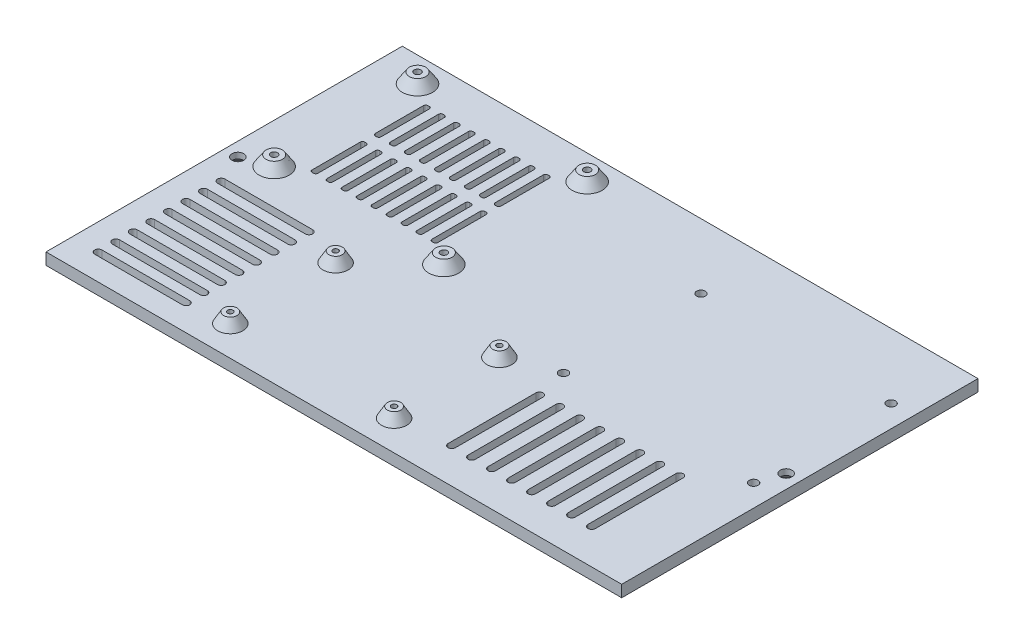
SolidWorks part; units mm, degrees
ref_plane "Front Plane" through (0, 0, 0) normal (0, 0, 1) x (1, 0, 0)
ref_plane "Top Plane" through (0, 0, 0) normal (0, 1, 0) x (1, 0, 0)
ref_plane "Right Plane" through (0, 0, 0) normal (1, 0, 0) x (0, 0, -1)
sketch "Sketch1" plane through (0, 0, 0) normal (0, 1, 0) x (1, 0, 0)
  line L1 (-98.4, 60.9) -> (98.4, 60.9)
  line L2 (-98.4, 60.9) -> (-98.4, -60.9)
  line L3 (-98.4, -60.9) -> (98.4, -60.9)
  line L4 (98.4, 60.9) -> (98.4, -60.9)
  line L5 (-98.4, 60.9) -> (98.4, -60.9) construction
  line L6 (-98.4, -60.9) -> (98.4, 60.9) construction
  point P0 (0, 0)
  dimension "D1" = 121.8
  dimension "D2" = 196.8
extrude "Boss-Extrude1" add sketch "Sketch1" along normal blind 4
sketch "Sketch2" plane through (0, 0, 0) normal (0, -1, 0) x (-1, 0, 0)
  line L0 (98.4, 60.9) -> (98.4, -60.9) construction
  circle A0 centre (93.7, 0) radius 2
  dimension "D2" = 4
  dimension "D1" = 4.7
extrude "Cut-Extrude1" cut sketch "Sketch2" against normal through all and the other way through all
hole_wizard "CSK for M4 Hex Socket Countersunk Head Screw3" positions "3DSketch1" profile "Sketch4" countersink size "M4" standard "DIN" end condition through all
sketch3d "3DSketch1"
  line L0 (-93.7, 4, 0) -> (-93.7, 0, 0) construction
  point P0 (-93.7, 0, 0)
sketch "Sketch4" plane through (-93.7, 0, 0) normal (1, 0, 0) x (0, 0, -1)
  line L0 (0, 0) -> (0, 4)
  line L1 (0, 4) -> (2, 4)
  line L2 (2, 4) -> (2, 2)
  line L3 (2, 2) -> (4, 0)
  line L5 (4, 0) -> (0, 0)
  line L6 (-2, 2) -> (-4, 0) construction
  line L11 (0, -6.35) -> (0, 107.95) construction
  dimension "Thru Hole Dia." = 4
  dimension "Thru Hole Depth" = 4
  dimension "Near C'Sink Dia." = 8
  dimension "Near C'Sink Angle" = 90
mirror "Mirror1" about plane through (0, 0, 0) normal (1, 0, 0) of "CSK for M4 Hex Socket Countersunk Head Screw3", "Cut-Extrude1"
sketch "Sketch6" plane through (0, 4, 0) normal (0, 1, 0) x (1, 0, 0)
  line L4 (98.4, 60.9) -> (-98.4, 60.9) construction
  line L5 (-98.4, 60.9) -> (-98.4, -60.9) construction
  circle A0 centre (-26.7, 3.4) radius 2.75
  circle A1 centre (-84.7, 3.4) radius 2.75
  circle A2 centre (-26.7, 52.4) radius 2.75
  circle A3 centre (-84.7, 52.4) radius 2.75
  line B0 (-88.2, 55.9) -> (-88.2, -0.1) construction
  line B1 (-88.2, -0.1) -> (-0.828, -0.1) construction
  line B2 (-0.828, -0.1) -> (-0.828, 55.9) construction
  line B3 (-0.828, 55.9) -> (-88.2, 55.9) construction
  circle B4 centre (-84.7, 52.4) radius 1.6
  circle B5 centre (-26.7, 52.4) radius 1.6
  circle B6 centre (-84.7, 3.4) radius 1.6
  circle B7 centre (-26.7, 3.4) radius 1.6
  dimension "D3" = 5.5
  dimension "D1" = 5
  dimension "D2" = 10.2
sketch_block_instance "Raspberry_Pi_3-1"
sketch_block "Raspberry_Pi_3" parameters "D11"=3.2, "D1"=87.372, "D2"=56, "D3"=3.5, "D4"=3.5, "D5"=3.5, "D6"=3.5, "D7"=3.5, "D8"=3.5, "D9"=58, "D10"=58
extrude "Boss-Extrude3" add sketch "Sketch6" along normal blind 3.5 contours A2 | A0 | A1 | A3
chamfer "Chamfer1" distance 2.4 angle 56 4 edges at (-84.7, 4, -49.65) (-26.7, 4, -49.65) (-84.7, 4, -0.65) (-26.7, 4, -0.65) first distance on face at (-84.7, 4, -49.65)
sketch "Sketch7" plane through (0, 7.5, 0) normal (0, 1, 0) x (1, 0, 0)
  circle A0 centre (-26.7, 3.4) radius 1.16
  circle A1 centre (-26.7, 52.4) radius 1.16
  circle A2 centre (-84.7, 52.4) radius 1.16
  circle A3 centre (-84.7, 3.4) radius 1.16
  dimension "D1" = 2.32
extrude "Cut-Extrude2" cut sketch "Sketch7" against normal blind 6.5
sketch "Sketch8" plane through (0, 4, 0) normal (0, 1, 0) x (1, 0, 0)
  circle A4 centre (-84.7, 3.4) radius 1.16 construction
  circle A5 centre (-26.7, 3.4) radius 1.16 construction
  circle A6 centre (-45.7, -14.6) radius 2.25
  circle A7 centre (10.3, -14.6) radius 2.25
  circle A8 centre (10.3, -50.6) radius 2.25
  circle A9 centre (-45.7, -50.6) radius 2.25
  circle B0 centre (-45.7, -50.6) radius 1
  circle B1 centre (-45.7, -14.6) radius 1
  circle B2 centre (10.3, -50.6) radius 1
  circle B3 centre (10.3, -14.6) radius 1
  line B4 (-47.7, -52.6) -> (-47.7, -12.6)
  line B5 (-47.7, -52.6) -> (12.3, -52.6)
  line B6 (-47.7, -12.6) -> (12.3, -12.6)
  line B7 (12.3, -52.6) -> (12.3, -12.6)
  line B8 (-47.7, -52.6) -> (12.3, -12.6) construction
  line B9 (12.3, -52.6) -> (-47.7, -12.6) construction
  dimension "D3" = 4.5
  dimension "D1" = 16
  dimension "D2" = 37
sketch_block_instance "Block1-1"
sketch_block "Block1" parameters "D3"=2, "D1"=36, "D2"=56, "D4"=27.8378, "D5"=16.8829, "D6"=53.5192, "D7"=78.3779
extrude "Boss-Extrude4" add sketch "Sketch8" along normal blind 3.5 contours A9 | A6 | A7 | A8
chamfer "Chamfer2" distance 2.05 angle 60 4 edges at (10.3, 4, 16.85) (10.3, 4, 52.85) (-45.7, 4, 52.85) (-45.7, 4, 16.85) first distance on face at (10.3, 4, 52.85)
sketch "Sketch9" plane through (0, 7.5, 0) normal (0, 1, 0) x (1, 0, 0)
  circle A0 centre (-45.7, -14.6) radius 0.93
  circle A1 centre (10.3, -14.6) radius 0.93
  circle A2 centre (10.3, -50.6) radius 0.93
  circle A3 centre (-45.7, -50.6) radius 0.93
  dimension "D1" = 1.86
extrude "Cut-Extrude3" cut sketch "Sketch9" against normal blind 6.5
sketch "Sketch10" plane through (0, 4, 0) normal (0, 1, 0) x (1, 0, 0)
  line L0 (98.4, 60.9) -> (-98.4, 60.9) construction
  line L1 (89.4, 60.7) -> (27.4, 60.7)
  line L2 (89.4, 60.7) -> (89.4, -30.3)
  line L3 (89.4, -30.3) -> (27.4, -30.3)
  line L4 (27.4, 60.7) -> (27.4, -30.3)
  line L5 (98.4, -60.9) -> (98.4, 60.9) construction
  circle A0 centre (25.9, 38.7) radius 1.5
  circle A1 centre (25.9, -8.3) radius 1.5
  circle A2 centre (90.9, -8.3) radius 1.5
  circle A3 centre (90.9, 38.7) radius 1.5
  dimension "D5" = 3
  dimension "D1" = 62
  dimension "D2" = 91
  dimension "D3" = 0.2
  dimension "D4" = 9
  dimension "D6" = 22
  dimension "D7" = 22
extrude "Cut-Extrude4" cut sketch "Sketch10" against normal through all contours A0 | A1 | A2 | A3 region at (90.9, 4, -38.7) region at (90.9, 4, 8.3) region at (25.9, 4, 8.3) region at (25.9, 4, -38.7)
sketch "Sketch11" plane through (0, 4, 0) normal (0, 1, 0) x (1, 0, 0)
  line L1 (-76.45, 47.7) -> (-75.95, 47.7)
  line L2 (-77.2, 46.95) -> (-77.2, 30.45)
  line L3 (-76.45, 29.7) -> (-75.95, 29.7)
  line L4 (-75.2, 46.95) -> (-75.2, 30.45)
  line L5 (-72.075, 46.95) -> (-72.075, 30.45)
  line L6 (-71.325, 47.7) -> (-70.825, 47.7)
  line L7 (-70.075, 46.95) -> (-70.075, 30.45)
  line L8 (-71.325, 29.7) -> (-70.825, 29.7)
  line L9 (-66.95, 46.95) -> (-66.95, 30.45)
  line L10 (-66.2, 47.7) -> (-65.7, 47.7)
  line L11 (-64.95, 46.95) -> (-64.95, 30.45)
  line L12 (-66.2, 29.7) -> (-65.7, 29.7)
  line L13 (-61.825, 46.95) -> (-61.825, 30.45)
  line L14 (-61.075, 47.7) -> (-60.575, 47.7)
  line L15 (-59.825, 46.95) -> (-59.825, 30.45)
  line L16 (-61.075, 29.7) -> (-60.575, 29.7)
  line L17 (-56.7, 46.95) -> (-56.7, 30.45)
  line L18 (-55.95, 47.7) -> (-55.45, 47.7)
  line L19 (-54.7, 46.95) -> (-54.7, 30.45)
  line L20 (-55.95, 29.7) -> (-55.45, 29.7)
  line L21 (-51.575, 46.95) -> (-51.575, 30.45)
  line L22 (-50.825, 47.7) -> (-50.325, 47.7)
  line L23 (-49.575, 46.95) -> (-49.575, 30.45)
  line L24 (-50.825, 29.7) -> (-50.325, 29.7)
  line L25 (-46.45, 46.95) -> (-46.45, 30.45)
  line L26 (-45.7, 47.7) -> (-45.2, 47.7)
  line L27 (-44.45, 46.95) -> (-44.45, 30.45)
  line L28 (-45.7, 29.7) -> (-45.2, 29.7)
  line L29 (-41.325, 46.95) -> (-41.325, 30.45)
  line L30 (-40.575, 47.7) -> (-40.075, 47.7)
  line L31 (-39.325, 46.95) -> (-39.325, 30.45)
  line L32 (-40.575, 29.7) -> (-40.075, 29.7)
  line L33 (-36.2, 46.95) -> (-36.2, 30.45)
  line L34 (-35.45, 47.7) -> (-34.95, 47.7)
  line L35 (-34.2, 46.95) -> (-34.2, 30.45)
  line L36 (-35.45, 29.7) -> (-34.95, 29.7)
  line L37 (-72.075, 25.35) -> (-72.075, 8.85)
  line L38 (-71.325, 26.1) -> (-70.825, 26.1)
  line L39 (-70.075, 25.35) -> (-70.075, 8.85)
  line L40 (-71.325, 8.1) -> (-70.825, 8.1)
  line L41 (-66.95, 25.35) -> (-66.95, 8.85)
  line L42 (-66.2, 26.1) -> (-65.7, 26.1)
  line L43 (-64.95, 25.35) -> (-64.95, 8.85)
  line L44 (-66.2, 8.1) -> (-65.7, 8.1)
  line L45 (-61.825, 25.35) -> (-61.825, 8.85)
  line L46 (-61.075, 26.1) -> (-60.575, 26.1)
  line L47 (-59.825, 25.35) -> (-59.825, 8.85)
  line L48 (-61.075, 8.1) -> (-60.575, 8.1)
  line L49 (-56.7, 25.35) -> (-56.7, 8.85)
  line L50 (-55.95, 26.1) -> (-55.45, 26.1)
  line L51 (-54.7, 25.35) -> (-54.7, 8.85)
  line L52 (-55.95, 8.1) -> (-55.45, 8.1)
  line L53 (-51.575, 25.35) -> (-51.575, 8.85)
  line L54 (-50.825, 26.1) -> (-50.325, 26.1)
  line L55 (-49.575, 25.35) -> (-49.575, 8.85)
  line L56 (-50.825, 8.1) -> (-50.325, 8.1)
  line L57 (-46.45, 25.35) -> (-46.45, 8.85)
  line L58 (-45.7, 26.1) -> (-45.2, 26.1)
  line L59 (-44.45, 25.35) -> (-44.45, 8.85)
  line L60 (-45.7, 8.1) -> (-45.2, 8.1)
  line L61 (-41.325, 25.35) -> (-41.325, 8.85)
  line L62 (-40.575, 26.1) -> (-40.075, 26.1)
  line L63 (-39.325, 25.35) -> (-39.325, 8.85)
  line L64 (-40.575, 8.1) -> (-40.075, 8.1)
  line L65 (-36.2, 25.35) -> (-36.2, 8.85)
  line L66 (-35.45, 26.1) -> (-34.95, 26.1)
  line L67 (-34.2, 25.35) -> (-34.2, 8.85)
  line L68 (-35.45, 8.1) -> (-34.95, 8.1)
  line L69 (-77.2, 25.35) -> (-77.2, 8.85)
  line L70 (-76.45, 26.1) -> (-75.95, 26.1)
  line L71 (-75.2, 25.35) -> (-75.2, 8.85)
  line L72 (-76.45, 8.1) -> (-75.95, 8.1)
  arc A0 (-75.95, 47.7) -> (-75.2, 46.95) centre (-75.95, 46.95) cw
  arc A1 (-76.45, 47.7) -> (-77.2, 46.95) centre (-76.45, 46.95) ccw
  arc A2 (-75.95, 29.7) -> (-75.2, 30.45) centre (-75.95, 30.45) ccw
  arc A3 (-77.2, 30.45) -> (-76.45, 29.7) centre (-76.45, 30.45) ccw
  arc A4 (-72.075, 30.45) -> (-71.325, 29.7) centre (-71.325, 30.45) ccw
  arc A5 (-71.325, 47.7) -> (-72.075, 46.95) centre (-71.325, 46.95) ccw
  arc A6 (-70.825, 47.7) -> (-70.075, 46.95) centre (-70.825, 46.95) cw
  arc A7 (-70.825, 29.7) -> (-70.075, 30.45) centre (-70.825, 30.45) ccw
  arc A8 (-66.95, 30.45) -> (-66.2, 29.7) centre (-66.2, 30.45) ccw
  arc A9 (-66.2, 47.7) -> (-66.95, 46.95) centre (-66.2, 46.95) ccw
  arc A10 (-65.7, 47.7) -> (-64.95, 46.95) centre (-65.7, 46.95) cw
  arc A11 (-65.7, 29.7) -> (-64.95, 30.45) centre (-65.7, 30.45) ccw
  arc A12 (-61.825, 30.45) -> (-61.075, 29.7) centre (-61.075, 30.45) ccw
  arc A13 (-61.075, 47.7) -> (-61.825, 46.95) centre (-61.075, 46.95) ccw
  arc A14 (-60.575, 47.7) -> (-59.825, 46.95) centre (-60.575, 46.95) cw
  arc A15 (-60.575, 29.7) -> (-59.825, 30.45) centre (-60.575, 30.45) ccw
  arc A16 (-56.7, 30.45) -> (-55.95, 29.7) centre (-55.95, 30.45) ccw
  arc A17 (-55.95, 47.7) -> (-56.7, 46.95) centre (-55.95, 46.95) ccw
  arc A18 (-55.45, 47.7) -> (-54.7, 46.95) centre (-55.45, 46.95) cw
  arc A19 (-55.45, 29.7) -> (-54.7, 30.45) centre (-55.45, 30.45) ccw
  arc A20 (-51.575, 30.45) -> (-50.825, 29.7) centre (-50.825, 30.45) ccw
  arc A21 (-50.825, 47.7) -> (-51.575, 46.95) centre (-50.825, 46.95) ccw
  arc A22 (-50.325, 47.7) -> (-49.575, 46.95) centre (-50.325, 46.95) cw
  arc A23 (-50.325, 29.7) -> (-49.575, 30.45) centre (-50.325, 30.45) ccw
  arc A24 (-46.45, 30.45) -> (-45.7, 29.7) centre (-45.7, 30.45) ccw
  arc A25 (-45.7, 47.7) -> (-46.45, 46.95) centre (-45.7, 46.95) ccw
  arc A26 (-45.2, 47.7) -> (-44.45, 46.95) centre (-45.2, 46.95) cw
  arc A27 (-45.2, 29.7) -> (-44.45, 30.45) centre (-45.2, 30.45) ccw
  arc A28 (-41.325, 30.45) -> (-40.575, 29.7) centre (-40.575, 30.45) ccw
  arc A29 (-40.575, 47.7) -> (-41.325, 46.95) centre (-40.575, 46.95) ccw
  arc A30 (-40.075, 47.7) -> (-39.325, 46.95) centre (-40.075, 46.95) cw
  arc A31 (-40.075, 29.7) -> (-39.325, 30.45) centre (-40.075, 30.45) ccw
  arc A32 (-36.2, 30.45) -> (-35.45, 29.7) centre (-35.45, 30.45) ccw
  arc A33 (-35.45, 47.7) -> (-36.2, 46.95) centre (-35.45, 46.95) ccw
  arc A34 (-34.95, 47.7) -> (-34.2, 46.95) centre (-34.95, 46.95) cw
  arc A35 (-34.95, 29.7) -> (-34.2, 30.45) centre (-34.95, 30.45) ccw
  arc A36 (-72.075, 8.85) -> (-71.325, 8.1) centre (-71.325, 8.85) ccw
  arc A37 (-71.325, 26.1) -> (-72.075, 25.35) centre (-71.325, 25.35) ccw
  arc A38 (-70.825, 26.1) -> (-70.075, 25.35) centre (-70.825, 25.35) cw
  arc A39 (-70.825, 8.1) -> (-70.075, 8.85) centre (-70.825, 8.85) ccw
  arc A40 (-66.95, 8.85) -> (-66.2, 8.1) centre (-66.2, 8.85) ccw
  arc A41 (-66.2, 26.1) -> (-66.95, 25.35) centre (-66.2, 25.35) ccw
  arc A42 (-65.7, 26.1) -> (-64.95, 25.35) centre (-65.7, 25.35) cw
  arc A43 (-65.7, 8.1) -> (-64.95, 8.85) centre (-65.7, 8.85) ccw
  arc A44 (-61.825, 8.85) -> (-61.075, 8.1) centre (-61.075, 8.85) ccw
  arc A45 (-61.075, 26.1) -> (-61.825, 25.35) centre (-61.075, 25.35) ccw
  arc A46 (-60.575, 26.1) -> (-59.825, 25.35) centre (-60.575, 25.35) cw
  arc A47 (-60.575, 8.1) -> (-59.825, 8.85) centre (-60.575, 8.85) ccw
  arc A48 (-56.7, 8.85) -> (-55.95, 8.1) centre (-55.95, 8.85) ccw
  arc A49 (-55.95, 26.1) -> (-56.7, 25.35) centre (-55.95, 25.35) ccw
  arc A50 (-55.45, 26.1) -> (-54.7, 25.35) centre (-55.45, 25.35) cw
  arc A51 (-55.45, 8.1) -> (-54.7, 8.85) centre (-55.45, 8.85) ccw
  arc A52 (-51.575, 8.85) -> (-50.825, 8.1) centre (-50.825, 8.85) ccw
  arc A53 (-50.825, 26.1) -> (-51.575, 25.35) centre (-50.825, 25.35) ccw
  arc A54 (-50.325, 26.1) -> (-49.575, 25.35) centre (-50.325, 25.35) cw
  arc A55 (-50.325, 8.1) -> (-49.575, 8.85) centre (-50.325, 8.85) ccw
  arc A56 (-46.45, 8.85) -> (-45.7, 8.1) centre (-45.7, 8.85) ccw
  arc A57 (-45.7, 26.1) -> (-46.45, 25.35) centre (-45.7, 25.35) ccw
  arc A58 (-45.2, 26.1) -> (-44.45, 25.35) centre (-45.2, 25.35) cw
  arc A59 (-45.2, 8.1) -> (-44.45, 8.85) centre (-45.2, 8.85) ccw
  arc A60 (-41.325, 8.85) -> (-40.575, 8.1) centre (-40.575, 8.85) ccw
  arc A61 (-40.575, 26.1) -> (-41.325, 25.35) centre (-40.575, 25.35) ccw
  arc A62 (-40.075, 26.1) -> (-39.325, 25.35) centre (-40.075, 25.35) cw
  arc A63 (-40.075, 8.1) -> (-39.325, 8.85) centre (-40.075, 8.85) ccw
  arc A64 (-36.2, 8.85) -> (-35.45, 8.1) centre (-35.45, 8.85) ccw
  arc A65 (-35.45, 26.1) -> (-36.2, 25.35) centre (-35.45, 25.35) ccw
  arc A66 (-34.95, 26.1) -> (-34.2, 25.35) centre (-34.95, 25.35) cw
  arc A67 (-34.95, 8.1) -> (-34.2, 8.85) centre (-34.95, 8.85) ccw
  arc A68 (-77.2, 8.85) -> (-76.45, 8.1) centre (-76.45, 8.85) ccw
  arc A69 (-76.45, 26.1) -> (-77.2, 25.35) centre (-76.45, 25.35) ccw
  arc A70 (-75.95, 26.1) -> (-75.2, 25.35) centre (-75.95, 25.35) cw
  arc A71 (-75.95, 8.1) -> (-75.2, 8.85) centre (-75.95, 8.85) ccw
  circle A72 centre (-26.7, 52.4) radius 1.16 construction
  circle A73 centre (-84.7, 3.4) radius 1.16 construction
  circle A74 centre (-84.7, 52.4) radius 1.16 construction
  circle A75 centre (-84.7, 52.4) radius 1.16 construction
  point P11 (-75.2, 47.7)
  point P14 (-77.2, 47.7)
  point P17 (-75.2, 29.7)
  point P20 (-77.2, 29.7)
  dimension "D5" = 0.75
  dimension "D1" = 2
  dimension "D2" = 18
  dimension "D3" = 4.7
  dimension "D4" = 7.5
  dimension "D8" = 7.5
  dimension "D9" = 4.7
  dimension "D6" = 9
  dimension "D7" = 2
extrude "Cut-Extrude5" cut sketch "Sketch11" against normal through all
sketch "Sketch12" plane through (0, 4, 0) normal (0, 1, 0) x (1, 0, 0)
  line L0 (-89.4, -10) -> (-59.4, -10) construction
  line L1 (-89.4, -8.75) -> (-59.4, -8.75)
  line L2 (-89.4, -11.25) -> (-59.4, -11.25)
  line L3 (-98.4, 60.9) -> (-98.4, -60.9) construction
  line L4 (-89.4, -17.25) -> (-59.4, -17.25)
  line L5 (-89.4, -14.75) -> (-59.4, -14.75)
  line L6 (-89.4, -16) -> (-59.4, -16) construction
  line L7 (-89.4, -23.25) -> (-59.4, -23.25)
  line L8 (-89.4, -20.75) -> (-59.4, -20.75)
  line L9 (-89.4, -22) -> (-59.4, -22) construction
  line L10 (-89.4, -29.25) -> (-59.4, -29.25)
  line L11 (-89.4, -26.75) -> (-59.4, -26.75)
  line L12 (-89.4, -28) -> (-59.4, -28) construction
  line L13 (-89.4, -35.25) -> (-59.4, -35.25)
  line L14 (-89.4, -32.75) -> (-59.4, -32.75)
  line L15 (-89.4, -34) -> (-59.4, -34) construction
  line L16 (-89.4, -41.25) -> (-59.4, -41.25)
  line L17 (-89.4, -38.75) -> (-59.4, -38.75)
  line L18 (-89.4, -40) -> (-59.4, -40) construction
  line L19 (-89.4, -47.25) -> (-59.4, -47.25)
  line L20 (-89.4, -44.75) -> (-59.4, -44.75)
  line L21 (-89.4, -46) -> (-59.4, -46) construction
  line L22 (-89.4, -53.25) -> (-59.4, -53.25)
  line L23 (-89.4, -50.75) -> (-59.4, -50.75)
  line L24 (-89.4, -52) -> (-59.4, -52) construction
  arc A0 (-89.4, -8.75) -> (-89.4, -11.25) centre (-89.4, -10) ccw
  arc A1 (-59.4, -11.25) -> (-59.4, -8.75) centre (-59.4, -10) ccw
  circle A2 centre (-93.7, 0) radius 2 construction
  arc A3 (-89.4, -14.75) -> (-89.4, -17.25) centre (-89.4, -16) ccw
  arc A4 (-59.4, -17.25) -> (-59.4, -14.75) centre (-59.4, -16) ccw
  arc A5 (-89.4, -20.75) -> (-89.4, -23.25) centre (-89.4, -22) ccw
  arc A6 (-59.4, -23.25) -> (-59.4, -20.75) centre (-59.4, -22) ccw
  arc A7 (-89.4, -26.75) -> (-89.4, -29.25) centre (-89.4, -28) ccw
  arc A8 (-59.4, -29.25) -> (-59.4, -26.75) centre (-59.4, -28) ccw
  arc A9 (-89.4, -32.75) -> (-89.4, -35.25) centre (-89.4, -34) ccw
  arc A10 (-59.4, -35.25) -> (-59.4, -32.75) centre (-59.4, -34) ccw
  arc A11 (-89.4, -38.75) -> (-89.4, -41.25) centre (-89.4, -40) ccw
  arc A12 (-59.4, -41.25) -> (-59.4, -38.75) centre (-59.4, -40) ccw
  arc A13 (-89.4, -44.75) -> (-89.4, -47.25) centre (-89.4, -46) ccw
  arc A14 (-59.4, -47.25) -> (-59.4, -44.75) centre (-59.4, -46) ccw
  arc A15 (-89.4, -50.75) -> (-89.4, -53.25) centre (-89.4, -52) ccw
  arc A16 (-59.4, -53.25) -> (-59.4, -50.75) centre (-59.4, -52) ccw
  point P2 (-74.4, -10)
  point P15 (-74.4, -16)
  point P22 (-74.4, -22)
  point P29 (-74.4, -28)
  point P36 (-74.4, -34)
  point P43 (-74.4, -40)
  point P50 (-74.4, -46)
  point P57 (-74.4, -52)
  dimension "D1" = 2.5
  dimension "D2" = 30
  dimension "D3" = 9
  dimension "D4" = 10
  dimension "D5" = 8
extrude "Cut-Extrude6" cut sketch "Sketch12" against normal through all
sketch "Sketch13" plane through (0, 4, 0) normal (0, 1, 0) x (1, 0, 0)
  line L0 (28.3, -18.9) -> (28.3, -48.9) construction
  line L1 (29.55, -18.9) -> (29.55, -48.9)
  line L2 (27.05, -18.9) -> (27.05, -48.9)
  line L3 (-98.4, -60.9) -> (98.4, -60.9) construction
  line L4 (33.8857, -18.9) -> (33.8857, -48.9)
  line L5 (36.3857, -18.9) -> (36.3857, -48.9)
  line L6 (35.1357, -18.9) -> (35.1357, -48.9) construction
  line L7 (40.7214, -18.9) -> (40.7214, -48.9)
  line L8 (43.2214, -18.9) -> (43.2214, -48.9)
  line L9 (41.9714, -18.9) -> (41.9714, -48.9) construction
  line L10 (47.5571, -18.9) -> (47.5571, -48.9)
  line L11 (50.0571, -18.9) -> (50.0571, -48.9)
  line L12 (48.8071, -18.9) -> (48.8071, -48.9) construction
  line L13 (54.3929, -18.9) -> (54.3929, -48.9)
  line L14 (56.8929, -18.9) -> (56.8929, -48.9)
  line L15 (55.6429, -18.9) -> (55.6429, -48.9) construction
  line L16 (61.2286, -18.9) -> (61.2286, -48.9)
  line L17 (63.7286, -18.9) -> (63.7286, -48.9)
  line L18 (62.4786, -18.9) -> (62.4786, -48.9) construction
  line L19 (68.0643, -18.9) -> (68.0643, -48.9)
  line L20 (70.5643, -18.9) -> (70.5643, -48.9)
  line L21 (69.3143, -18.9) -> (69.3143, -48.9) construction
  line L22 (74.9, -18.9) -> (74.9, -48.9)
  line L23 (77.4, -18.9) -> (77.4, -48.9)
  line L24 (76.15, -18.9) -> (76.15, -48.9) construction
  line L25 (98.4, -60.9) -> (98.4, 60.9) construction
  arc A0 (29.55, -18.9) -> (27.05, -18.9) centre (28.3, -18.9) ccw
  arc A1 (27.05, -48.9) -> (29.55, -48.9) centre (28.3, -48.9) ccw
  circle A2 centre (10.3, -50.6) radius 0.93 construction
  arc A3 (36.3857, -18.9) -> (33.8857, -18.9) centre (35.1357, -18.9) ccw
  arc A4 (33.8857, -48.9) -> (36.3857, -48.9) centre (35.1357, -48.9) ccw
  arc A5 (43.2214, -18.9) -> (40.7214, -18.9) centre (41.9714, -18.9) ccw
  arc A6 (40.7214, -48.9) -> (43.2214, -48.9) centre (41.9714, -48.9) ccw
  arc A7 (50.0571, -18.9) -> (47.5571, -18.9) centre (48.8071, -18.9) ccw
  arc A8 (47.5571, -48.9) -> (50.0571, -48.9) centre (48.8071, -48.9) ccw
  arc A9 (56.8929, -18.9) -> (54.3929, -18.9) centre (55.6429, -18.9) ccw
  arc A10 (54.3929, -48.9) -> (56.8929, -48.9) centre (55.6429, -48.9) ccw
  arc A11 (63.7286, -18.9) -> (61.2286, -18.9) centre (62.4786, -18.9) ccw
  arc A12 (61.2286, -48.9) -> (63.7286, -48.9) centre (62.4786, -48.9) ccw
  arc A13 (70.5643, -18.9) -> (68.0643, -18.9) centre (69.3143, -18.9) ccw
  arc A14 (68.0643, -48.9) -> (70.5643, -48.9) centre (69.3143, -48.9) ccw
  arc A15 (77.4, -18.9) -> (74.9, -18.9) centre (76.15, -18.9) ccw
  arc A16 (74.9, -48.9) -> (77.4, -48.9) centre (76.15, -48.9) ccw
  point P2 (28.3, -33.9)
  point P15 (35.1357, -33.9)
  point P22 (41.9714, -33.9)
  point P29 (48.8071, -33.9)
  point P36 (55.6429, -33.9)
  point P43 (62.4786, -33.9)
  point P50 (69.3143, -33.9)
  point P57 (76.15, -33.9)
  dimension "D1" = 2.5
  dimension "D2" = 30
  dimension "D3" = 12
  dimension "D4" = 18
  dimension "D6" = 21
  dimension "D5" = 8
extrude "Cut-Extrude7" cut sketch "Sketch13" against normal through all
